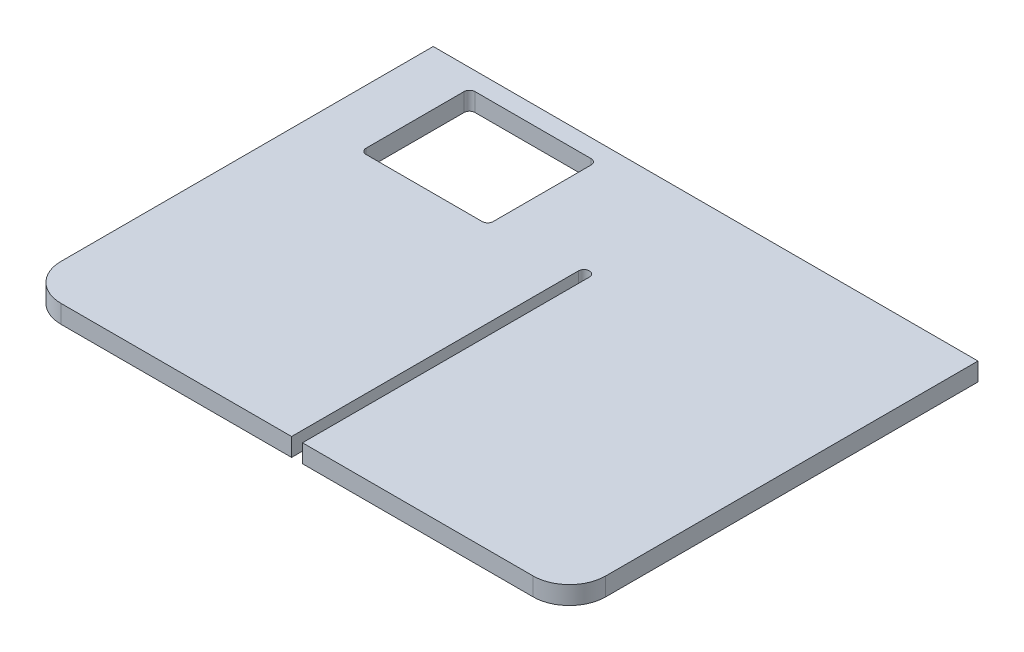
SolidWorks part; units mm, degrees
ref_plane "Ebene vorne" through (0, 0, 0) normal (0, 0, 1) x (1, 0, 0)
ref_plane "Ebene oben" through (0, 0, 0) normal (0, 1, 0) x (1, 0, 0)
ref_plane "Ebene rechts" through (0, 0, 0) normal (1, 0, 0) x (0, 0, -1)
sketch "Skizze1" plane through (0, 0, 0) normal (0, 1, 0) x (1, 0, 0)
  line L0 (150, 75) -> (150, 150)
  line L1 (0, -75) -> (150, -75)
  line L2 (0, -75) -> (0, 75)
  line L3 (150, 150) -> (0, 150)
  line L4 (150, -75) -> (150, 75)
  line L5 (0, 150) -> (0, 75)
  line L6 (0, 0) -> (150, 0) construction
  dimension "D1" = 150
  dimension "D2" = 75
extrude "Linear austragen1" add sketch "Skizze1" along normal blind 10
fillet "Verrundung1" radius 20 1 edges at (150, 5, 75)
mirror "Spiegeln2" about plane through (0, 10, -150) normal (1, 0, 0) of "Verrundung1", "Linear austragen1"
sketch "Skizze3" plane through (0, 0, 0) normal (0, 1, 0) x (-1, 0, 0)
  line L1 (120, -140) -> (50, -140)
  line L2 (120, -140) -> (120, -80)
  line L3 (120, -80) -> (50, -80)
  line L4 (50, -140) -> (50, -80)
  line L8 (150, 55) -> (150, -150) construction
  line L9 (-150, -150) -> (150, -150) construction
  dimension "D1" = 30
  dimension "D2" = 10
  dimension "D3" = 70
  dimension "D4" = 60
extrude "Schnitt-Linear austragen1" cut sketch "Skizze3" along normal through all
fillet "Verrundung2" radius 3 4 edges at (-120, 5, -80) (-50, 5, -80) (-120, 5, -140) (-50, 5, -140)
sketch "Skizze4" plane through (0, 0, 0) normal (0, -1, 0) x (1, 0, 0)
  line L0 (-3, 75) -> (-3, -83)
  line L1 (3, 75) -> (3, -83)
  line L2 (0, 0) -> (-3, 0) construction
  line L3 (0, 0) -> (3, 0) construction
  line L5 (-3, 75) -> (3, 75)
  line L6 (-130, 75) -> (130, 75) construction
  line L7 (-117, -80) -> (-53, -80) construction
  arc A1 (-3, -83) -> (3, -83) centre (0, -83) ccw
  dimension "D2" = 3
  dimension "D1" = 6
extrude "Schnitt-Linear austragen2" cut sketch "Skizze4" against normal blind 10
